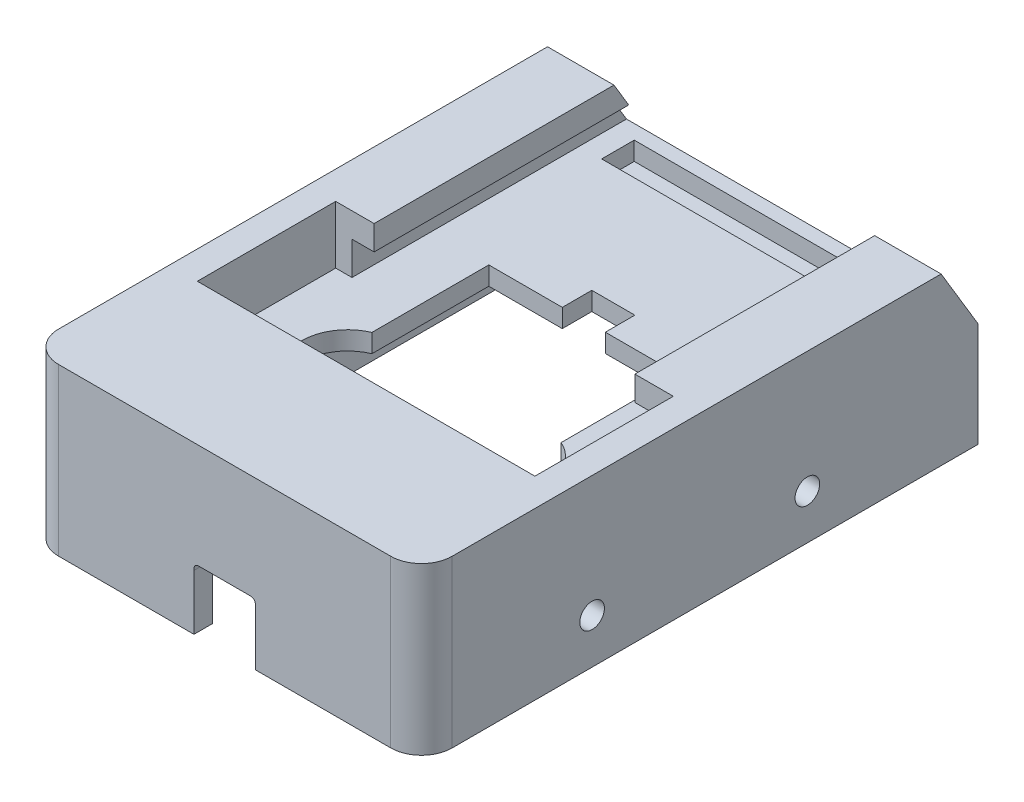
SolidWorks part; units mm, degrees
ref_plane "Front Plane" through (0, 0, 0) normal (0, 0, 1) x (1, 0, 0)
ref_plane "Top Plane" through (0, 0, 0) normal (0, 1, 0) x (1, 0, 0)
ref_plane "Right Plane" through (0, 0, 0) normal (1, 0, 0) x (0, 0, -1)
sketch "Sketch1" plane through (0, 0, 0) normal (0, 1, 0) x (1, 0, 0)
  line L1 (0, 0) -> (64, 0)
  line L2 (0, 0) -> (0, 84.5)
  line L3 (0, 84.5) -> (64, 84.5)
  line L4 (64, 0) -> (64, 84.5)
  dimension "D1" = 64
  dimension "D2" = 84.5
extrude "Boss-Extrude1" add sketch "Sketch1" along normal blind 27
fillet "Fillet1" radius 5 4 edges at (0, 13.5, -84.5) (0, 13.5, 0) (64, 13.5, -84.5) (64, 13.5, 0)
sketch "Sketch2" plane through (0, 27, 0) normal (0, 1, 0) x (1, 0, 0)
  line L0 (59, 84.5) -> (5, 84.5) construction
  line L1 (10.8, 84.5) -> (53.2, 84.5)
  line L2 (10.8, 84.5) -> (10.8, 23)
  line L3 (10.8, 23) -> (53.2, 23)
  line L4 (53.2, 84.5) -> (53.2, 23)
  line L5 (0, 79.5) -> (0, 5) construction
  line L6 (64, 5) -> (64, 79.5) construction
  dimension "D1" = 10.8
  dimension "D2" = 10.8
  dimension "D3" = 61.5
extrude "Cut-Extrude1" cut sketch "Sketch2" against normal blind 9.4
sketch "Sketch3" plane through (0, 0, -84.5) normal (0, 0, -1) x (-1, 0, 0)
  line L1 (-53.2, 17.6) -> (-56.8, 17.6)
  line L2 (-53.2, 17.6) -> (-53.2, 23)
  line L3 (-53.2, 23) -> (-56.8, 23)
  line L4 (-56.8, 17.6) -> (-56.8, 23)
  line L5 (-10.8, 17.6) -> (-7.2, 17.6)
  line L6 (-10.8, 17.6) -> (-10.8, 23)
  line L7 (-10.8, 23) -> (-7.2, 23)
  line L8 (-7.2, 17.6) -> (-7.2, 23)
  dimension "D1" = 3.6
  dimension "D2" = 5.4
extrude "Cut-Extrude2" cut sketch "Sketch3" against normal blind 61.5
sketch "Sketch4" plane through (0, 17.6, 0) normal (0, 1, 0) x (1, 0, 0)
  line L0 (7.2, 23) -> (56.8, 23) construction
  line L1 (46.7, 23) -> (17.3, 23)
  line L2 (46.7, 23) -> (46.7, 49.4)
  line L3 (46.7, 49.4) -> (17.3, 49.4)
  line L4 (17.3, 23) -> (17.3, 49.4)
  line L5 (7.2, 23) -> (17.3, 23)
  line L6 (46.7, 23) -> (56.8, 23) construction
  line L7 (35.5, 54.2) -> (56.8, 54.2) construction
  line L8 (35.5, 49.4) -> (28.5, 49.4)
  line L9 (35.5, 49.4) -> (35.5, 54.2)
  line L10 (35.5, 54.2) -> (28.5, 54.2)
  line L11 (28.5, 49.4) -> (28.5, 54.2)
  line L12 (56.8, 23) -> (56.8, 84.5) construction
  line L13 (28.5, 54.2) -> (7.2, 54.2) construction
  line L14 (7.2, 23) -> (7.2, 84.5) construction
  line M15 (7.2, 23) -> (56.8, 23)
  dimension "D1" = 26.4
  dimension "D2" = 29.4
  dimension "D3" = 4.8
  dimension "D4" = 7
extrude "Cut-Extrude3" cut sketch "Sketch4" against normal blind 61.5 contours L4 L2 L3 M15 | L11 L3 L9 L10 region at (32, 17.6, -36.2) region at (32, 17.6, -51.8)
sketch "Sketch5" plane through (0, 0, 0) normal (0, -1, 0) x (1, 0, 0)
  line L0 (3, -3) -> (0, -3)
  line L1 (3, -3) -> (61, -3)
  line L2 (3, -3) -> (3, -81.5)
  line L3 (3, -81.5) -> (61, -81.5)
  line L4 (61, -3) -> (61, -81.5)
  line L5 (0, -79.5) -> (0, -5) construction
  line L6 (3, -3) -> (3, 0) construction
  line L7 (5, 0) -> (59, 0) construction
  line L9 (61, -3) -> (64, -3) construction
  line L10 (64, -5) -> (64, -79.5) construction
  line L12 (3, -81.5) -> (3, -84.5) construction
  line L13 (59, -84.5) -> (5, -84.5) construction
  line M17 (28.5, -49.4) -> (17.3, -49.4)
  line M18 (17.3, -49.4) -> (17.3, -23)
  line M19 (17.3, -23) -> (46.7, -23)
  line M20 (46.7, -23) -> (46.7, -49.4)
  line M21 (46.7, -49.4) -> (35.5, -49.4)
  line M22 (35.5, -49.4) -> (35.5, -54.2)
  line M23 (35.5, -54.2) -> (28.5, -54.2)
  line M24 (28.5, -54.2) -> (28.5, -49.4)
  dimension "D1" = 3
extrude "Cut-Extrude4" cut sketch "Sketch5" against normal blind 14.6 contours L4 L1 L2 L3 M24 M17 M18 M19 M20 M21 M22 M23 region at (32, 0, -3.976)
fillet "Fillet2" radius 5 4 edges at (61, 7.3, -81.5) (61, 7.3, -3) (3, 7.3, -81.5) (3, 7.3, -3)
sketch "Sketch6" plane through (0, 14.6, 0) normal (0, -1, 0) x (1, 0, 0)
  line L0 (17.3, -23) -> (46.7, -23) construction
  line L1 (8, -3) -> (56, -3)
  line L3 (8, -20) -> (56, -20)
  line L5 (8, -20) -> (3, -20)
  line L6 (3, -8) -> (3, -76.5) construction
  line L7 (3, -20) -> (3, -8)
  line L8 (56, -20) -> (61, -20)
  line L9 (61, -8) -> (61, -76.5) construction
  line L10 (61, -20) -> (61, -8)
  arc A0 (8, -3) -> (3, -8) centre (8, -8) ccw construction
  arc A1 (8, -3) -> (3, -8) centre (8, -8) ccw
  arc A2 (61, -8) -> (56, -3) centre (56, -8) ccw
  dimension "D1" = 3
extrude "Cut-Extrude5" cut sketch "Sketch6" against normal blind 9.4
sketch "Sketch7" plane through (0, 0, 0) normal (0, 0, 1) x (1, 0, 0)
  line L0 (5, 0) -> (59, 0) construction
  line L1 (27, 0) -> (37, 0)
  line L2 (27, 0) -> (27, 10)
  line L3 (27, 10) -> (37, 10)
  line L4 (37, 0) -> (37, 10)
  line L6 (5, 0) -> (27, 0) construction
  line L7 (37, 0) -> (59, 0) construction
  dimension "D1" = 10
  dimension "D2" = 10
extrude "Cut-Extrude6" cut sketch "Sketch7" against normal blind 10
fillet "Fillet3" radius 1 2 edges at (37, 10, -1.5) (27, 10, -1.5) curvature continuous yes
sketch "Sketch8" plane through (0, 27, 0) normal (0, 1, 0) x (1, 0, 0)
  line L1 (10.8, 23) -> (4.55, 23)
  line L2 (10.8, 23) -> (10.8, 36.5)
  line L3 (10.8, 36.5) -> (4.55, 36.5)
  line L4 (4.55, 23) -> (4.55, 36.5)
  line L5 (53.2, 23) -> (59.45, 23)
  line L6 (53.2, 23) -> (53.2, 36.5)
  line L7 (53.2, 36.5) -> (59.45, 36.5)
  line L8 (59.45, 23) -> (59.45, 36.5)
  dimension "D1" = 6.25
  dimension "D2" = 13.5
extrude "Cut-Extrude8" cut sketch "Sketch8" against normal blind 9.4
sketch "Sketch9" plane through (0, 17.6, 0) normal (0, 1, 0) x (1, 0, 0)
  line L0 (17.3, 49.4) -> (17.3, 57.4)
  line L1 (46.7, 49.4) -> (46.7, 57.4)
  line L2 (28.5, 57.4) -> (28.5, 62.2)
  line L3 (35.5, 57.4) -> (35.5, 62.2)
  line L4 (35.5, 62.2) -> (28.5, 62.2)
  line L5 (17.3, 57.4) -> (28.5, 57.4)
  line L6 (46.7, 57.4) -> (35.5, 57.4)
  line L7 (17.3, 49.4) -> (46.7, 49.4)
  dimension "D1" = 8
extrude "Cut-Extrude9" cut sketch "Sketch9" against normal blind 10
sketch "Sketch10" plane through (0, 27, 0) normal (0, 1, 0) x (1, 0, 0)
  line L0 (4.55, 36.5) -> (4.55, 45.5)
  line L1 (4.55, 45.5) -> (10.8, 45.5)
  line L2 (10.8, 84.5) -> (10.8, 36.5) construction
  line L3 (10.8, 45.5) -> (10.8, 36.5)
  line L4 (10.8, 36.5) -> (4.55, 36.5)
  line L6 (53.2, 36.5) -> (59.45, 36.5)
  line L7 (53.2, 36.5) -> (53.2, 45.5)
  line L8 (53.2, 45.5) -> (59.45, 45.5)
  line L9 (59.45, 36.5) -> (59.45, 45.5)
  dimension "D1" = 9
  dimension "D2" = 6.25
  dimension "D3" = 9
extrude "Cut-Extrude10" cut sketch "Sketch10" against normal blind 9.4
sketch "Sketch11" plane through (0, 17.6, 0) normal (0, 1, 0) x (1, 0, 0)
  line L1 (28.5, 62.2) -> (35.5, 62.2)
  line L2 (28.5, 62.2) -> (28.5, 63.2)
  line L3 (28.5, 63.2) -> (35.5, 63.2)
  line L4 (35.5, 62.2) -> (35.5, 63.2)
  line L5 (17.3, 57.4) -> (46.7, 57.4)
  line L6 (17.3, 57.4) -> (17.3, 58.4)
  line L7 (17.3, 58.4) -> (46.7, 58.4)
  line L8 (46.7, 57.4) -> (46.7, 58.4)
  dimension "D1" = 1
  dimension "D2" = 1
extrude "Cut-Extrude11" cut sketch "Sketch11" against normal blind 9.4
sketch "Sketch12" plane through (0, 14.6, 0) normal (0, -1, 0) x (1, 0, 0)
  line L0 (17.3, -58.4) -> (17.3, -23) construction
  line L1 (46.7, -23) -> (17.3, -23)
  line L2 (46.7, -23) -> (46.7, -30.5)
  line L3 (46.7, -30.5) -> (17.3, -30.5)
  line L4 (17.3, -23) -> (17.3, -30.5)
  dimension "D1" = 7.5
extrude "Boss-Extrude2" add sketch "Sketch12" against normal blind 3
sketch "Sketch13" plane through (0, 17.6, 0) normal (0, 1, 0) x (1, 0, 0)
  line L1 (17.3, 58.4) -> (16.55, 58.4)
  line L2 (17.3, 58.4) -> (17.3, 30.5)
  line L3 (17.3, 30.5) -> (16.55, 30.5)
  line L4 (16.55, 58.4) -> (16.55, 30.5)
  line L5 (46.7, 58.4) -> (47.45, 58.4)
  line L6 (46.7, 58.4) -> (46.7, 30.5)
  line L7 (46.7, 30.5) -> (47.45, 30.5)
  line L8 (47.45, 58.4) -> (47.45, 30.5)
  dimension "D1" = 0.75
extrude "Cut-Extrude12" cut sketch "Sketch13" against normal blind 3
sketch "Sketch15" plane through (0, 14.6, 0) normal (0, -1, 0) x (1, 0, 0)
  line L0 (47.45, -32.5) -> (44.5, -32.5) construction
  line L1 (47.45, -30.5) -> (47.45, -58.4) construction
  line L2 (44.5, -32.5) -> (19.5, -32.5) construction
  line L3 (19.5, -32.5) -> (16.55, -32.5) construction
  line L4 (16.55, -58.4) -> (16.55, -30.5) construction
  circle A0 centre (44.5, -32.5) radius 7.3699
  circle A1 centre (19.5, -32.5) radius 7.5
  dimension "D3" = 15
  dimension "D1" = 25
  dimension "D2" = 2
extrude "Cut-Extrude13" cut sketch "Sketch15" against normal blind 3
sketch "Sketch16" plane through (64, 0, 0) normal (1, 0, 0) x (0, 0, -1)
  line L0 (84.5, 27) -> (84.5, 17)
  line L1 (84.5, 27) -> (84.5, 0) construction
  line L3 (84.5, 27) -> (90.5, 17)
  line L4 (90.5, 17) -> (90.5, 0)
  line L5 (90.5, 0) -> (84.5, 0)
  line L6 (84.5, 0) -> (84.5, 17)
extrude "Boss-Extrude3" add sketch "Sketch16" against normal blind 64
sketch "Sketch17" plane through (0, 27, 0) normal (0, 1, 0) x (1, 0, 0)
  line L0 (64, 84.5) -> (64, 79.5)
  line L1 (64, 5) -> (64, 79.5) construction
  line L2 (64, 79.5) -> (59, 84.5)
  line L3 (59, 84.5) -> (64, 84.5)
  line L4 (0, 79.5) -> (5, 84.5)
  line L5 (5, 84.5) -> (0, 84.5)
  line L6 (0, 84.5) -> (0, 79.5)
  arc A0 (64, 79.5) -> (59, 84.5) centre (59, 79.5) ccw construction
extrude "Boss-Extrude4" add sketch "Sketch17" against normal blind 27
sketch "Sketch18" plane through (0, 17.6, 0) normal (0, 1, 0) x (1, 0, 0)
  line L1 (7.2, 84.5) -> (56.8, 84.5)
  line L2 (7.2, 84.5) -> (7.2, 92.0651)
  line L3 (7.2, 92.0651) -> (56.8, 92.0651)
  line L4 (56.8, 84.5) -> (56.8, 92.0651)
extrude "Cut-Extrude16" cut sketch "Sketch18" along normal blind 5.4
sketch "Sketch19" plane through (0, 0, -84.5) normal (0, 0, 1) x (1, 0, 0)
  line L1 (53.2, 27) -> (10.8, 27)
  line L2 (53.2, 27) -> (53.2, 23)
  line L3 (53.2, 23) -> (10.8, 23)
  line L4 (10.8, 27) -> (10.8, 23)
extrude "Cut-Extrude17" cut sketch "Sketch19" against normal blind 5.4
sketch "Sketch20" plane through (0, 17.6, 0) normal (0, 1, 0) x (1, 0, 0)
  line L0 (53.2, 84.5) -> (53.2, 86.9) construction
  line L2 (10.8, 84.5) -> (10.8, 87.8)
  line L3 (10.8, 87.8) -> (53.2, 87.8)
  line L4 (53.2, 84.5) -> (53.2, 87.8)
  line L7 (10.8, 84.5) -> (10.8, 82.5)
  line L8 (10.8, 82.5) -> (53.2, 82.5)
  line L9 (53.2, 84.5) -> (53.2, 82.5)
  dimension "D1" = 3.3
  dimension "D2" = 2
extrude "Cut-Extrude18" cut sketch "Sketch20" against normal blind 3
sketch "Sketch21" plane through (61, 0, 0) normal (-1, 0, 0) x (0, 0, 1)
  line L0 (-84.5, 27) -> (-5, 27) construction
  line L1 (-90.5, 0) -> (-5, 0) construction
  circle A0 centre (-62.75, 7.3) radius 2
  circle A1 centre (-27.75, 7.3) radius 2
  point P6 (-44.75, 27)
  point P7 (0, 0)
  point P8 (0, 0)
  point P9 (-37.512, 15.2253)
  point P10 (0, 0)
  dimension "D3" = 4
  dimension "D4" = 4
  dimension "D1" = 18
  dimension "D2" = 35
  dimension "D5" = 7.3
extrude "Cut-Extrude19" cut sketch "Sketch21" against normal blind 10
